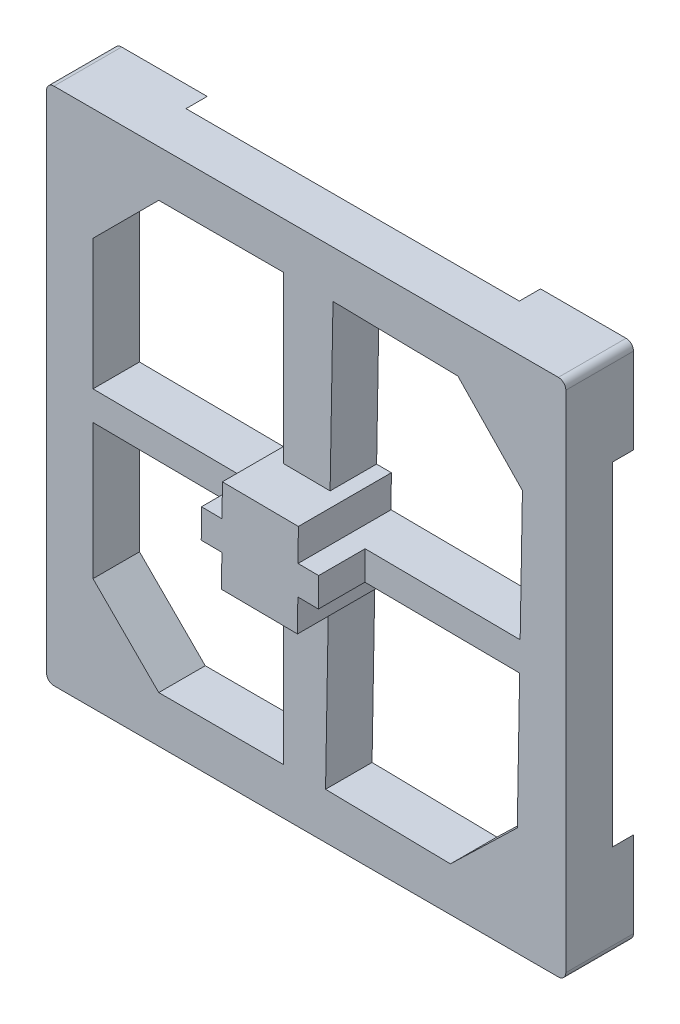
SolidWorks part; units mm, degrees
material "PET"
ref_plane "Front Plane" through (0, 0, 0) normal (0, 0, 1) x (1, 0, 0)
ref_plane "Top Plane" through (0, 0, 0) normal (0, 1, 0) x (1, 0, 0)
ref_plane "Right Plane" through (0, 0, 0) normal (1, 0, 0) x (0, 0, -1)
sketch "Sketch1" plane through (0, 0, 0) normal (0, 0, 1) x (1, 0, 0)
  line L0 (-97.6376, 73.8886) -> (-94.4626, 73.8886)
  line L2 (-94.4626, 73.8886) -> (-97.6376, 70.7136)
  line L4 (-97.6376, 70.7136) -> (-97.6376, 73.8886)
  line L5 (-88.773, 73.8886) -> (-88.773, 56.1594) construction
  line L7 (-88.773, 65.024) -> (-79.9084, 65.024) construction
  line L9 (-79.9084, 70.7136) -> (-79.9084, 73.8886)
  line L10 (-83.0834, 73.8886) -> (-79.9084, 70.7136)
  line L11 (-79.9084, 73.8886) -> (-83.0834, 73.8886)
  line L12 (-79.9084, 56.1594) -> (-83.0834, 56.1594)
  line L13 (-83.0834, 56.1594) -> (-79.9084, 59.3344)
  line L14 (-79.9084, 59.3344) -> (-79.9084, 56.1594)
  line L15 (-97.6376, 59.3344) -> (-97.6376, 56.1594)
  line L16 (-94.4626, 56.1594) -> (-97.6376, 59.3344)
  line L17 (-97.6376, 56.1594) -> (-94.4626, 56.1594)
extrude "Boss-Extrude1" add sketch "Sketch1" along normal blind 6.35
sketch "Sketch2" plane through (0, 0, 6.35) normal (0, 0, 1) x (1, 0, 0)
  line L0 (-88.773, 73.8886) -> (-88.773, 56.1594)
  line L1 (-97.6376, 73.8886) -> (-79.9084, 73.8886)
  line L2 (-97.6376, 73.8886) -> (-97.6376, 56.1594)
  line L3 (-97.6376, 56.1594) -> (-79.9084, 56.1594)
  line L4 (-79.9084, 73.8886) -> (-79.9084, 56.1594)
  line L5 (-97.6376, 73.8886) -> (-79.9084, 56.1594) construction
  line L6 (-97.6376, 56.1594) -> (-79.9084, 73.8886) construction
  line L7 (-97.6376, 65.024) -> (-79.9084, 65.024)
  point P4 (-88.773, 65.024)
extrude "Extrude-Thin1" add sketch "Sketch2" along normal blind 1.5875 separate body thin contours L0 | L7 thin type mid plane wall 1.5875
extrude "Extrude-Thin2" add sketch "Sketch2<3>" along normal blind 1.5875 thin contours L2 L3 L4 L1 thin type one direction reverse wall 1.5875
sketch "Sketch2<3>" plane through (0, 0, 6.35) normal (0, 0, 1) x (1, 0, 0) same geometry as "Sketch2"
sketch "Sketch6" plane through (0, 0, 7.9375) normal (0, 0, 1) x (1, 0, 0)
  line L0 (-89.5668, 65.8177) -> (-87.9793, 64.2302) construction
  circle A0 centre (-88.773, 65.024) radius 1.5875
  dimension "D1" = 3.175
extrude "Boss-Extrude3" add sketch "Sketch6" against normal up to surface (1.5875 mm away) up to face at (-89.0329, 65.1705, 6.35)
hole_wizard "#56 (0.0465) Diameter Hole1" positions "Sketch5" profile "Sketch4" hole size "#56" standard "ANSI Inch" end condition through all
sketch "Sketch5" plane through (0, 0, 7.9375) normal (0, 0, 1) x (1, 0, 0)
  point P6 (-88.773, 65.024)
sketch "Sketch4" plane through (-88.773, 65.024, 7.9375) normal (1, 0, 0) x (0, -1, 0)
  line L0 (0, 0) -> (0, 7.9375)
  line L1 (0, 7.9375) -> (0.5905, 7.9375)
  line L2 (0.5905, 7.9375) -> (0.5905, 0)
  line L5 (0.5905, 0) -> (0, 0)
  line L11 (0, -6.35) -> (0, 107.95) construction
  dimension "Thru Hole Dia." = 1.1811
  dimension "Thru Hole Depth" = 7.9375
chamfer "Chamfer1" distance 1.5875 angle 45 8 edges at (-82.2897, 56.9531, 6.35) (-80.7022, 58.5406, 6.35) (-80.7022, 71.5073, 6.35) (-82.2897, 73.0948, 6.35) (-95.2564, 56.9531, 6.35) (-96.8439, 58.5406, 6.35)
fillet "Fillet2" radius 0.762 20 edges at (-89.5668, 72.3011, 7.1437) (-96.0501, 72.3011, 6.35) (-96.0501, 65.8177, 7.1437) (-90.1478, 65.8177, 7.1437) (-89.5668, 66.3988, 7.1437) (-96.0501, 64.2302, 7.1437) (-96.0501, 57.7469, 6.35) (-89.5668, 57.7469, 7.1437) (-89.5668, 63.6492, 7.1437) (-87.9793, 63.6492, 7.1437) (-87.9793, 57.7469, 7.1437) (-81.4959, 57.7469, 6.35) (-81.4959, 64.2302, 7.1437) (-87.3982, 64.2302, 7.1437) (-87.3982, 65.8177, 7.1437) (-81.4959, 65.8177, 7.1437) (-81.4959, 72.3011, 6.35) (-87.9793, 72.3011, 7.1437) (-87.9793, 66.3988, 7.1437) (-90.1478, 64.2302, 7.1437)
fillet "Fillet3" [suppressed] radius 0.762
fillet "Fillet4" radius 0.254 4 edges at (-79.9084, 56.1594, 3.9688) (-79.9084, 73.8886, 3.9688) (-97.6376, 73.8886, 3.9688) (-97.6376, 56.1594, 3.9688)
sketch "Sketch7" plane through (0, 0, 7.9375) normal (0, 0, 1) x (1, 0, 0)
  line L4 (-97.3836, 56.1594) -> (-80.1624, 56.1594)
  line L5 (-79.9084, 56.4134) -> (-79.9084, 73.6346)
  line L6 (-80.1624, 73.8886) -> (-97.3836, 73.8886)
  line L7 (-97.6376, 73.6346) -> (-97.6376, 56.4134)
  line L8 (-97.3836, 56.1594) -> (-80.1624, 56.1594)
  line L9 (-79.9084, 56.4134) -> (-79.9084, 73.6346)
  line L10 (-80.1624, 73.8886) -> (-97.3836, 73.8886)
  line L11 (-97.6376, 73.6346) -> (-97.6376, 56.4134)
  arc A4 (-80.1624, 56.1594) -> (-79.9084, 56.4134) centre (-80.1624, 56.4134) ccw
  arc A5 (-79.9084, 73.6346) -> (-80.1624, 73.8886) centre (-80.1624, 73.6346) ccw
  arc A6 (-97.3836, 73.8886) -> (-97.6376, 73.6346) centre (-97.3836, 73.6346) ccw
  arc A7 (-97.6376, 56.4134) -> (-97.3836, 56.1594) centre (-97.3836, 56.4134) ccw
  arc A8 (-80.1624, 56.1594) -> (-79.9084, 56.4134) centre (-80.1624, 56.4134) ccw
  arc A9 (-79.9084, 73.6346) -> (-80.1624, 73.8886) centre (-80.1624, 73.6346) ccw
  arc A10 (-97.3836, 73.8886) -> (-97.6376, 73.6346) centre (-97.3836, 73.6346) ccw
  arc A11 (-97.6376, 56.4134) -> (-97.3836, 56.1594) centre (-97.3836, 56.4134) ccw
  dimension "D1" = 0
extrude "Cut-Extrude1" cut sketch "Sketch7" against normal up to surface (5.6262 mm away)
sketch "Sketch8" plane through (0, 0, 2.3113) normal (0, 0, -1) x (-1, 0, 0)
  line L0 (79.9084, 70.7136) -> (79.9084, 73.6346) construction
  line L1 (94.4626, 73.8886) -> (97.3836, 73.8886) construction
  line L2 (97.6376, 59.3344) -> (97.6376, 56.4134) construction
  line L3 (83.0834, 56.1594) -> (80.1624, 56.1594) construction
  line L4 (79.9084, 56.4134) -> (79.9084, 73.6346)
  line L5 (80.1624, 73.8886) -> (97.3836, 73.8886)
  line L6 (97.6376, 73.6346) -> (97.6376, 56.4134)
  line L7 (97.3836, 56.1594) -> (80.1624, 56.1594)
  arc A0 (80.1624, 73.8886) -> (79.9084, 73.6346) centre (80.1624, 73.6346) ccw construction
  arc A1 (97.6376, 73.6346) -> (97.3836, 73.8886) centre (97.3836, 73.6346) ccw construction
  arc A2 (97.3836, 56.1594) -> (97.6376, 56.4134) centre (97.3836, 56.4134) ccw construction
  arc A3 (79.9084, 56.4134) -> (80.1624, 56.1594) centre (80.1624, 56.4134) ccw construction
  arc A4 (80.1624, 73.8886) -> (79.9084, 73.6346) centre (80.1624, 73.6346) ccw
  arc A5 (97.6376, 73.6346) -> (97.3836, 73.8886) centre (97.3836, 73.6346) ccw
  arc A6 (97.3836, 56.1594) -> (97.6376, 56.4134) centre (97.3836, 56.4134) ccw
  arc A7 (79.9084, 56.4134) -> (80.1624, 56.1594) centre (80.1624, 56.4134) ccw
  point P0 (97.2073, 56.1594)
  point P4 (79.9084, 73.8886)
  point P5 (79.9084, 56.1594)
extrude "Boss-Extrude4" add sketch "Sketch8" along normal blind 1.5875
sketch "Sketch9" plane through (0, 0, 2.3113) normal (0, 0, 1) x (1, 0, 0)
  line L21 (-90.0552, 65.552) -> (-90.7584, 65.5581)
  line L22 (-90.0456, 66.652) -> (-90.0552, 65.552)
  line L23 (-87.4521, 66.6293) -> (-90.0456, 66.652)
  line L24 (-87.4617, 65.5294) -> (-87.4521, 66.6293)
  line L25 (-86.7586, 65.5232) -> (-87.4617, 65.5294)
  line L26 (-90.0552, 65.552) -> (-90.7584, 65.5581)
  line L27 (-90.0456, 66.652) -> (-90.0552, 65.552)
  line L28 (-87.4521, 66.6293) -> (-90.0456, 66.652)
  line L29 (-87.4617, 65.5294) -> (-87.4521, 66.6293)
  line L30 (-86.7586, 65.5232) -> (-87.4617, 65.5294)
  line L41 (-86.7586, 65.5232) -> (-86.7672, 64.5297)
  line L42 (-90.7584, 65.5581) -> (-90.7671, 64.5646)
  line L46 (-90.7671, 64.5646) -> (-90.0639, 64.5584)
  line L47 (-90.0639, 64.5584) -> (-90.0735, 63.4585)
  line L48 (-90.0735, 63.4585) -> (-87.48, 63.4359)
  line L49 (-87.48, 63.4359) -> (-87.4704, 64.5358)
  line L50 (-87.4704, 64.5358) -> (-86.7672, 64.5297)
  line L51 (-90.7671, 64.5646) -> (-90.0639, 64.5584)
  line L52 (-90.0639, 64.5584) -> (-90.0735, 63.4585)
  line L53 (-90.0735, 63.4585) -> (-87.48, 63.4359)
  line L54 (-87.48, 63.4359) -> (-87.4704, 64.5358)
  line L55 (-87.4704, 64.5358) -> (-86.7672, 64.5297)
  dimension "D1" = 0.2032
  dimension "D2" = 0.2032
extrude "Boss-Extrude5" add sketch "Sketch9" along normal blind 1.5875
sketch "Sketch10" plane through (0, 0, 0.7238) normal (0, 0, -1) x (-1, 0, 0)
  line L0 (89.5426, 63.4539) -> (89.5426, 57.7469)
  line L1 (86.7586, 65.5232) -> (87.4617, 65.5294)
  line L2 (87.4617, 65.5294) -> (87.4521, 66.6293)
  line L3 (87.4521, 66.6293) -> (87.9552, 66.6337)
  line L4 (88.0109, 63.4405) -> (87.48, 63.4359)
  line L5 (87.48, 63.4359) -> (87.4704, 64.5358)
  line L6 (87.4704, 64.5358) -> (86.7672, 64.5297)
  line L7 (87.9552, 66.6337) -> (87.8565, 72.2864)
  line L8 (90.7671, 64.5646) -> (90.0639, 64.5584) construction
  line L9 (90.7584, 65.5581) -> (96.0501, 65.6043)
  line L11 (90.7671, 64.5646) -> (96.0501, 64.6107)
  line L13 (90.0552, 65.552) -> (90.7584, 65.5581) construction
  line L15 (88.7489, 66.6407) -> (88.7768, 63.4472) construction
  line L16 (83.741, 57.7469) -> (93.805, 57.7469)
  line L17 (93.805, 57.7469) -> (96.0501, 59.992)
  line L18 (96.0501, 59.992) -> (96.0501, 70.056)
  line L19 (96.0501, 70.056) -> (93.805, 72.3011)
  line L20 (93.805, 72.3011) -> (83.741, 72.3011)
  line L21 (83.741, 72.3011) -> (81.4959, 70.056)
  line L22 (81.4959, 70.056) -> (81.4959, 59.992)
  line L23 (81.4959, 59.992) -> (83.741, 57.7469)
  line L24 (89.5426, 57.7469) -> (93.805, 57.7469)
  line L25 (93.805, 57.7469) -> (96.0501, 59.992)
  line L26 (96.0501, 59.992) -> (96.0501, 64.6107)
  line L27 (96.0501, 70.056) -> (93.805, 72.3011)
  line L28 (93.805, 72.3011) -> (89.5426, 72.3011)
  line L32 (87.4521, 66.6293) -> (90.0456, 66.652) construction
  line L33 (90.0735, 63.4585) -> (87.48, 63.4359) construction
  line L34 (96.0501, 65.6043) -> (96.0501, 70.056)
  line L35 (89.5426, 66.6476) -> (89.5426, 72.3011)
  line L36 (88.7628, 65.0439) -> (86.7629, 65.0265) construction
  line L37 (86.7672, 64.5297) -> (86.7586, 65.5232) construction
  line L38 (81.4669, 65.4771) -> (81.3892, 69.9281)
  line L39 (83.5947, 72.212) -> (87.8565, 72.2864)
  line L40 (81.3892, 69.9281) -> (83.5947, 72.212)
  line L41 (81.5648, 59.8656) -> (81.4842, 64.4836)
  line L42 (83.8487, 57.66) -> (81.5648, 59.8656)
  line L43 (90.0639, 64.5584) -> (90.7671, 64.5646)
  line L44 (90.0735, 63.4585) -> (90.0639, 64.5584)
  line L45 (87.48, 63.4359) -> (90.0735, 63.4585)
  line L46 (87.4704, 64.5358) -> (87.48, 63.4359)
  line L47 (86.7672, 64.5297) -> (87.4704, 64.5358)
  line L48 (86.7586, 65.5232) -> (86.7672, 64.5297)
  line L49 (87.4617, 65.5294) -> (86.7586, 65.5232)
  line L50 (87.4521, 66.6293) -> (87.4617, 65.5294)
  line L51 (90.0456, 66.652) -> (87.4521, 66.6293)
  line L52 (90.0552, 65.552) -> (90.0456, 66.652)
  line L53 (90.7584, 65.5581) -> (90.0552, 65.552)
  line L54 (90.7671, 64.5646) -> (90.7584, 65.5581)
  line L55 (90.0639, 64.5584) -> (90.7671, 64.5646)
  line L56 (90.0735, 63.4585) -> (90.0639, 64.5584)
  line L57 (89.5426, 63.4539) -> (90.0735, 63.4585)
  line L63 (90.0456, 66.652) -> (89.5426, 66.6476)
  line L64 (90.0552, 65.552) -> (90.0456, 66.652)
  line L65 (90.7584, 65.5581) -> (90.0552, 65.552)
  line L67 (88.1105, 57.7344) -> (83.8487, 57.66)
  line L68 (86.7672, 64.5297) -> (81.4842, 64.4836)
  line L69 (86.7586, 65.5232) -> (81.4669, 65.4771)
  line L70 (88.0109, 63.4405) -> (88.1105, 57.7344)
  dimension "D2" = 0.7937
  dimension "D1" = 1.5875
  dimension "D3" = 0
extrude "Cut-Extrude2" cut sketch "Sketch10" against normal through all
